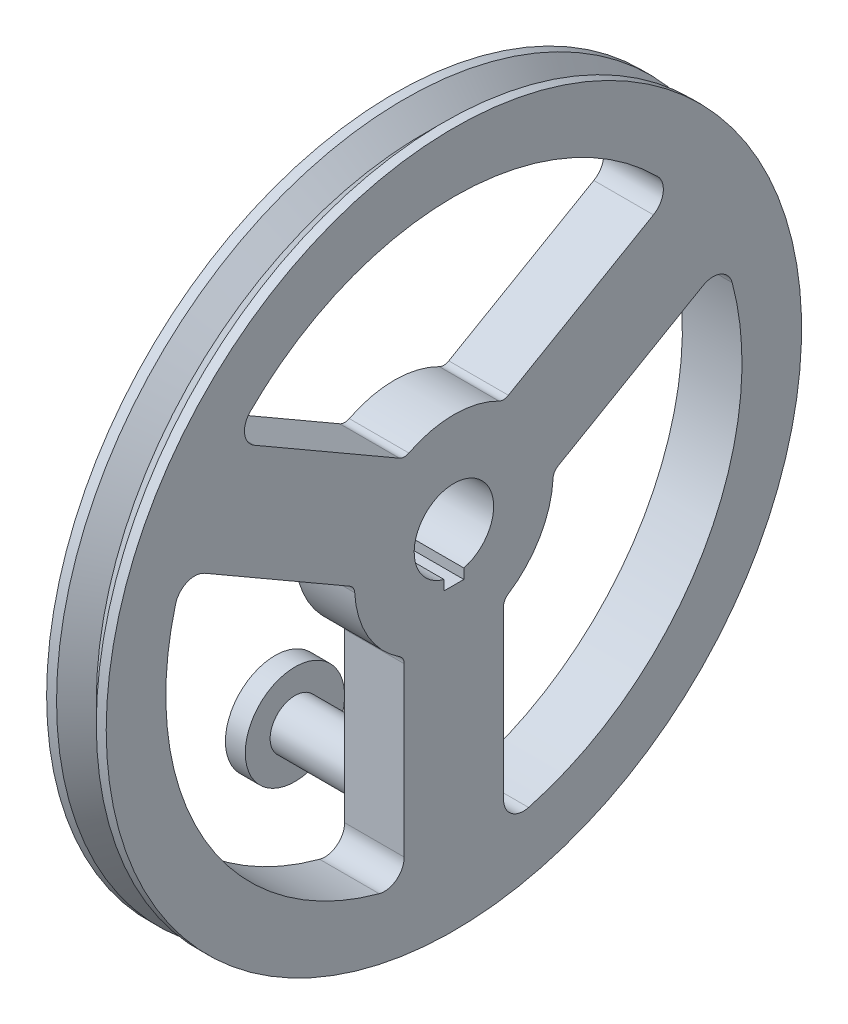
SolidWorks part; units mm, degrees
ref_plane "Front Plane" through (0, 0, 0) normal (0, 0, 1) x (1, 0, 0)
ref_plane "Top Plane" through (0, 0, 0) normal (0, 1, 0) x (1, 0, 0)
ref_plane "Right Plane" through (0, 0, 0) normal (1, 0, 0) x (0, 0, -1)
sketch "Sketch1" plane through (0, 0, 0) normal (0, 1, 0) x (1, 0, 0)
  line L0 (0, 0) -> (37.2314, 0) construction
  line L5 (-15, 175) -> (-15, 145)
  line L6 (-15, 145) -> (15, 145)
  line L7 (15, 145) -> (15, 175)
  line L8 (15, 175) -> (10, 175)
  line L9 (10, 175) -> (0, 165)
  line L10 (0, 165) -> (-10, 175)
  line L11 (-10, 175) -> (-15, 175)
  line L12 (15, 145) -> (15, 0) construction
  line L13 (-15, 145) -> (-15, 0) construction
  line L14 (-15, 0) -> (0, 0) construction
  line L15 (-15, 50) -> (15, 50)
  line L16 (-15, 20) -> (15, 20)
  line L17 (15, 20) -> (15, 50)
  line L18 (-15, 20) -> (-15, 50)
  line L19 (15, 0) -> (15, 20)
  line L20 (-15, 0) -> (-15, 20)
  point P12 (0, 145)
  point P25 (15, 50)
  point P29 (-15, 50)
  dimension "D1" = 30
  dimension "D2" = 145
  dimension "D3" = 175
  dimension "D4" = 5
  dimension "D5" = 10
  dimension "D7" = 50
  dimension "D8" = 20
revolve "Revolve1" add sketch "Sketch1" angle 360 mid plane about L0 region at (0, 0, -158.5417) region at (0, 0, -35)
sketch "Sketch2" plane through (0, 0, 0) normal (1, 0, 0) x (0, 0, -1)
  line L0 (0, 0) -> (0, 175) construction
  line L1 (25, -46.0977) -> (25, -130.384)
  line L2 (-25, -46.0977) -> (-25, -130.384)
  line L3 (-52.4218, 1.3982) -> (-125.4159, 43.5414)
  line L4 (-27.4218, 44.6995) -> (-100.4159, 86.8427)
  line L5 (27.4218, 44.6995) -> (100.4159, 86.8427)
  line L6 (52.4218, 1.3982) -> (125.4159, 43.5414)
  circle A0 centre (0, 0) radius 175 construction
  arc A2 (-27.2727, -41.907) -> (-25, -46.0977) centre (-30, -46.0977) cw
  circle A3 centre (0, 0) radius 145 construction
  circle A4 centre (0, 0) radius 175
  arc A7 (25, -130.384) -> (37.5926, -140.0421) centre (35, -130.384) ccw
  arc A8 (-25, -130.384) -> (-37.5926, -140.0421) centre (-35, -130.384) cw
  arc A9 (-22.6562, 44.5724) -> (-27.4218, 44.6995) centre (-24.9218, 49.0296) cw
  arc A10 (-49.9289, -2.6654) -> (-52.4218, 1.3982) centre (-54.9218, -2.9319) ccw
  arc A11 (-100.4159, 86.8427) -> (-102.4837, 102.5772) centre (-95.4159, 95.5029) cw
  arc A12 (-125.4159, 43.5414) -> (-140.0763, 37.4649) centre (-130.4159, 34.8811) ccw
  arc A13 (49.9289, -2.6654) -> (52.4218, 1.3982) centre (54.9218, -2.9319) cw
  arc A14 (22.6562, 44.5724) -> (27.4218, 44.6995) centre (24.9218, 49.0296) ccw
  arc A15 (125.4159, 43.5414) -> (140.0763, 37.4649) centre (130.4159, 34.8811) cw
  arc A16 (100.4159, 86.8427) -> (102.4837, 102.5772) centre (95.4159, 95.5029) ccw
  arc A17 (140.0763, 37.4649) -> (102.4837, 102.5772) centre (0, 0) ccw
  arc A18 (-37.5926, -140.0421) -> (37.5926, -140.0421) centre (0, 0) ccw
  arc A19 (-22.6562, 44.5724) -> (-49.9289, -2.6654) centre (0, 0) ccw
  arc A20 (-27.2727, -41.907) -> (27.2727, -41.907) centre (0, 0) ccw
  arc A21 (22.6562, 44.5724) -> (49.9117, -2.9702) centre (0, 0) cw
  circle A22 centre (0, 0) radius 50 construction
  arc A23 (27.2727, -41.907) -> (25, -46.0977) centre (30, -46.0977) ccw
  arc A24 (-140.0763, 37.4649) -> (-102.4837, 102.5772) centre (0, 0) cw
  circle A25 centre (0, 0) radius 50
  circle A26 centre (0, 0) radius 50
  circle A27 centre (0, 0) radius 175
  circle A28 centre (0, 0) radius 145
  point P49 (0, 0)
  dimension "D2" = 0
  dimension "D3" = 20
  dimension "D6" = 5
  dimension "D1" = 50
  dimension "D5" = 49.9117
  dimension "D7" = 0
  dimension "D4" = 3
extrude "Boss-Extrude1" add sketch "Sketch2" along normal mid plane 30 contours A19 A9 L4 A11 A12 L3 A10 | A23 A20 A2 L2 A8 A18 A7 L1 | A14 A21 A13 L6 A15 A17 A16 L5 region at (0, -96.6523, 0) region at (0, 48.3261, 83.7033) region at (0, 48.3261, -83.7033)
sketch "Sketch3" plane through (-15, 0, 0) normal (-1, 0, 0) x (0, 0, 1)
  circle A0 centre (0, -125) radius 25
  circle A1 centre (0, -125) radius 12.5
  dimension "D1" = 50
  dimension "D2" = 25
  dimension "D3" = 125
extrude "Boss-Extrude2" add sketch "Sketch3" along normal blind 50 contours A1
extrude "Boss-Extrude3" add sketch "Sketch3<3>" along normal blind 10 from surface contours A0 A1 | A1 region at (-15, -125, -24.2929) region at (-15, -125, 0) starting at face at (-65, -125, 12.5)
sketch "Sketch3<3>" plane through (-15, 0, 0) normal (-1, 0, 0) x (0, 0, 1) same geometry as "Sketch3"
sketch "Sketch4" plane through (-15, 0, 0) normal (-1, 0, 0) x (0, 0, 1)
  line L0 (0, 0) -> (0, 175) construction
  line L1 (5, -19.3649) -> (5, -24.3649)
  line L2 (5, -24.3649) -> (-5, -24.3649)
  line L3 (-5, -19.3649) -> (-5, -24.3649)
  circle A0 centre (0, 0) radius 175 construction
  circle A1 centre (0, 0) radius 20 construction
  arc A2 (-5, -19.3649) -> (5, -19.3649) centre (0, 0) ccw
  point P11 (0, -24.3649)
  circle M30 centre (0, 0) radius 20
  dimension "D1" = 5
  dimension "D2" = 5
extrude "Cut-Extrude1" cut sketch "Sketch4" against normal through all contours L3 L2 L1 M30 region at (-15, -22.0734, 0)
